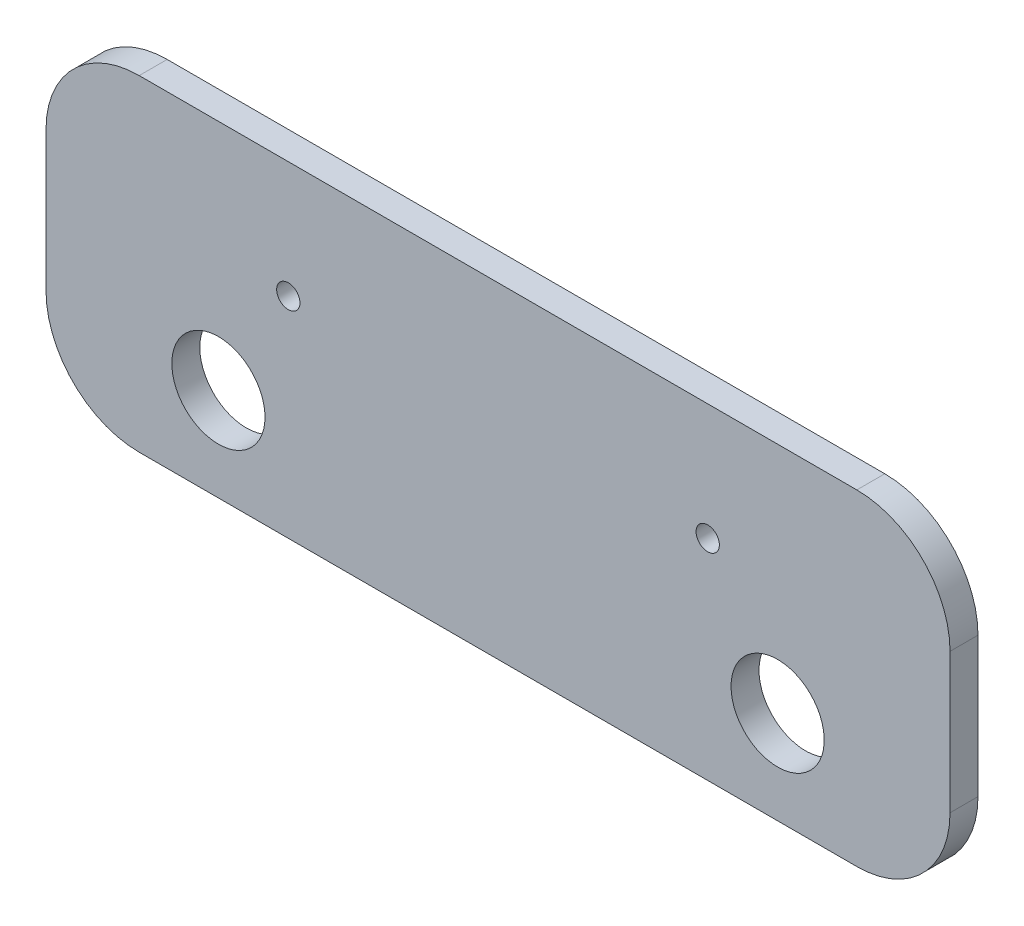
SolidWorks part; units mm, degrees
ref_plane "前视基准面" through (0, 0, 0) normal (0, 0, 1) x (1, 0, 0)
ref_plane "上视基准面" through (0, 0, 0) normal (0, 1, 0) x (1, 0, 0)
ref_plane "右视基准面" through (0, 0, 0) normal (1, 0, 0) x (0, 0, -1)
sketch "草图1" plane through (0, 0, 0) normal (0, 0, 1) x (1, 0, 0)
  line L1 (-45.5, -17.5) -> (45.5, -17.5)
  line L2 (-45.5, -17.5) -> (-45.5, 17.5)
  line L3 (-45.5, 17.5) -> (45.5, 17.5)
  line L4 (45.5, -17.5) -> (45.5, 17.5)
  line L5 (-45.5, -17.5) -> (45.5, 17.5) construction
  line L6 (-45.5, 17.5) -> (45.5, -17.5) construction
  point P0 (0, 0)
  dimension "D1" = 91
  dimension "D2" = 35
extrude "凸台-拉伸2" add sketch "草图1" along normal blind 3
sketch "草图2" plane through (0, 0, 0) normal (0, 0, -1) x (-1, 0, 0)
  circle A0 centre (-22.5, 5) radius 1.25
  circle A1 centre (22.5, 5) radius 1.25
extrude "切除-拉伸1" cut sketch "草图2" against normal blind 3
sketch "草图3" plane through (0, 0, 0) normal (0, 0, -1) x (-1, 0, 0)
  line L0 (45.5, 17.5) -> (45.5, -17.5) construction
  line L1 (-45.5, 17.5) -> (45.5, 17.5)
  line L2 (-45.5, 17.5) -> (-45.5, 14.5)
  line L3 (-45.5, 14.5) -> (45.5, 14.5)
  line L4 (45.5, 17.5) -> (45.5, 14.5)
  dimension "D1" = 3
extrude "凸台-拉伸3" add sketch "草图3" along normal blind 12
sketch "草图4" plane through (45.5, 0, 0) normal (1, 0, 0) x (0, 0, -1)
  line L0 (12, 17.5) -> (24, 17.5)
  line L1 (24, 17.5) -> (24, -17.5)
  line L2 (24, -17.5) -> (-3, -17.5)
  line L3 (-3, -17.5) -> (-3, 17.5)
  line L4 (-3, -17.5) -> (-3, 17.5) construction
  line L5 (-3, 17.5) -> (12, 17.5) construction
  line L6 (-3, 17.5) -> (12, 17.5)
extrude "凸台-拉伸4" add sketch "草图4" along normal blind 3
sketch "草图6" plane through (45.5, 0, 0) normal (-1, 0, 0) x (0, 0, 1)
  circle A0 centre (-20, 9.5) radius 1.25
  circle A1 centre (-20, -15.5) radius 1.25
extrude "切除-拉伸2" cut sketch "草图6" against normal blind 3
sketch "草图7" plane through (-45.5, 0, 0) normal (-1, 0, 0) x (0, 0, 1)
  line L1 (-24, 17.5) -> (3, 17.5)
  line L2 (-24, 17.5) -> (-24, -17.5)
  line L3 (-24, -17.5) -> (3, -17.5)
  line L4 (3, 17.5) -> (3, -17.5)
extrude "凸台-拉伸5" add sketch "草图7" along normal blind 3
sketch "草图8" plane through (-48.5, 0, 0) normal (-1, 0, 0) x (0, 0, 1)
  circle A0 centre (-20, 9.5) radius 1.25
  circle A1 centre (-20, -15.5) radius 1.25
extrude "切除-拉伸3" cut sketch "草图8" against normal blind 3
sketch "草图9" plane through (0, 0, 0) normal (0, 0, -1) x (-1, 0, 0)
  line L0 (-104.5404, 43.4878) -> (97.1357, 67.9972)
  line L1 (-104.5404, 43.4878) -> (-87.5871, -96.0127)
  line L2 (97.1357, 67.9972) -> (114.0891, -71.5033)
  line L3 (-87.5871, -96.0127) -> (114.0891, -71.5033)
extrude "切除-拉伸4" cut sketch "草图9" along normal blind 57.6696
sketch "草图10" plane through (0, 0, 3) normal (0, 0, 1) x (1, 0, 0)
  line L0 (0, -17.5) -> (-30, -17.5)
  line L1 (-48.5, -17.5) -> (48.5, -17.5) construction
  circle A0 centre (-30, -7.5) radius 5
  circle A1 centre (30, -7.5) radius 5
extrude "切除-拉伸5" cut sketch "草图10" against normal blind 57.6696 contours A0 | A1
fillet "圆角1" radius 10 4 edges at (48.5, 17.5, 1.5) (48.5, -17.5, 1.5) (-48.5, 17.5, 1.5) (-48.5, -17.5, 1.5)
